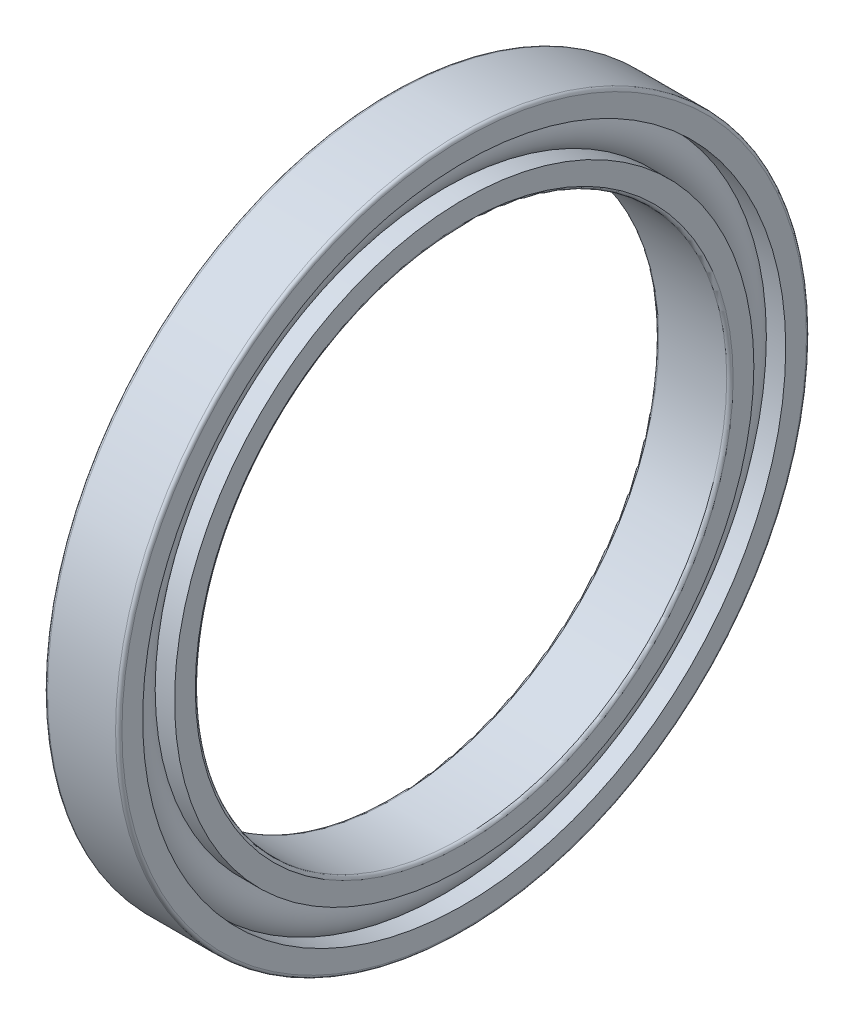
SolidWorks part; units mm, degrees
ref_plane "Plane1" through (0, 0, 0) normal (0, 0, 1) x (1, 0, 0)
ref_plane "Plane2" through (0, 0, 0) normal (0, 1, 0) x (1, 0, 0)
ref_plane "Plane3" through (0, 0, 0) normal (1, 0, 0) x (0, 0, -1)
sketch "Clipboard" plane through (0, 0, 0) normal (0, 0, 1) x (1, 0, 0)
  line L0 (-10, 0) -> (10, 0) construction
  line L1 (0, 0) -> (22.3471, -0.7804)
  line L2 (0, 0) -> (28.7325, 1.0034)
  line L3 (0, 0) -> (22.3471, -0.7804)
  line L4 (0, 0) -> (-22.3573, -0.3902)
  dimension "BallCLRad" = 28.75
sketch "CagSpiSke" plane through (0, 0, 0) normal (0, 0, 1) x (1, 0, 0)
  line L0 (0.225, 28.375) -> (0.225, 29.125)
  line L1 (0.225, 29.125) -> (-0.225, 29.125)
  line L2 (-0.225, 29.125) -> (-0.225, 28.375)
  line L3 (-0.225, 28.375) -> (0.225, 28.375)
  line L4 (-20.6375, 0) -> (20.6375, 0) construction
  line L5 (0, 0) -> (0, 23.7692) construction
  dimension "OD" = 58.25
  dimension "ID" = 56.75
revolve "CageSpine" add sketch "CagSpiSke" angle 0.001 about L4 reverse direction yes
ref_axis "Axis1" through (-50, 0, 0) along (1, 0, 0)
sketch "CagBalSke" plane through (0, 0, 0) normal (0, 0, 1) x (1, 0, 0)
  line L0 (-2.475, 28.75) -> (2.475, 28.75)
  line L1 (-1.905, 28.75) -> (1.905, 28.75) construction
  line L2 (-10, 0) -> (10, 0) construction
  line L3 (0, 0) -> (0, 24) construction
  arc A0 (2.475, 28.75) -> (-2.475, 28.75) centre (0, 28.75) cw
  dimension "BallCLRad" = 28.75
revolve "CageBall" [suppressed] add sketch "CagBalSke" angle 360 about L1 reverse direction yes
pattern_circular "CageBalls" [suppressed] count 2 every 180 about axis through (-50, 0, 0) along (1, 0, 0)
sketch "CagTrmODSke" plane through (0, 0, 0) normal (0, 0, 1) x (1, 0, 0)
  line L0 (2.476, 29.125) -> (2.476, 31.226)
  line L1 (2.476, 31.226) -> (-2.476, 31.226)
  line L2 (-2.476, 31.226) -> (-2.476, 29.125)
  line L3 (-2.476, 29.125) -> (2.476, 29.125)
  line L4 (-20.6375, 0) -> (20.6375, 0) construction
  line L5 (0, 0) -> (0, 25) construction
  dimension "Width" = 4.952
  dimension "ID" = 58.25
  dimension "OD" = 62.452
revolve "CageTrimOD" [suppressed] cut sketch "CagTrmODSke" angle 360 about L4 reverse direction yes
sketch "CagTrmIDSke" plane through (0, 0, 0) normal (0, 0, 1) x (1, 0, 0)
  line L0 (2.476, 26.276) -> (2.476, 28.375)
  line L1 (2.476, 28.375) -> (-2.476, 28.375)
  line L2 (-2.476, 28.375) -> (-2.476, 26.276)
  line L3 (-2.476, 26.276) -> (2.476, 26.276)
  line L4 (-20.6375, 0) -> (20.6375, 0) construction
  line L5 (0, 0) -> (0, 25) construction
  dimension "Width" = 4.952
  dimension "ID" = 52.552
  dimension "OD" = 56.75
revolve "CageTrimID" [suppressed] cut sketch "CagTrmIDSke" angle 360 about L4 reverse direction yes
sketch "BalSimSke" plane through (0, 0, 0) normal (0, 0, 1) x (1, 0, 0)
  line L0 (-10, 0) -> (10, 0) construction
  line L1 (-10, 28.75) -> (10, 28.75) construction
  line L2 (0, 0) -> (0, 23) construction
  circle A0 centre (0, 28.75) radius 2.25
  dimension "BallCLRad" = 28.75
  dimension "Ball_diameter" = 4.5
revolve "BallsSimplified" add sketch "BalSimSke" angle 360 about L0
sketch "BalDetSke" plane through (0, 0, 0) normal (0, 0, 1) x (1, 0, 0)
  line L0 (-2.25, 28.75) -> (2.25, 28.75)
  line L1 (-1.905, 28.75) -> (1.905, 28.75) construction
  line L2 (0, 0) -> (0, 25) construction
  arc A0 (2.25, 28.75) -> (-2.25, 28.75) centre (0, 28.75) cw
  dimension "BallCLRad" = 28.75
  dimension "Ball_diameter" = 4.5
revolve "BallDetailed" [suppressed] add sketch "BalDetSke" angle 360 about L1 reverse direction yes
sketch "InnRacSke" plane through (0, 0, 0) normal (0, 0, 1) x (1, 0, 0)
  line L0 (-1.6434, 27.25) -> (-3.5, 27.25)
  line L1 (-3.5, 27.25) -> (-3.5, 25.3)
  line L2 (-3.2, 25) -> (3.2, 25)
  line L3 (3.5, 25.3) -> (3.5, 27.25)
  line L4 (3.5, 27.25) -> (1.6434, 27.25)
  line L5 (-20.6375, 0) -> (20.6375, 0) construction
  line L6 (0, 0) -> (0, 30) construction
  arc A0 (-3.5, 25.3) -> (-3.2, 25) centre (-3.2, 25.3) ccw
  arc A1 (3.2, 25) -> (3.5, 25.3) centre (3.2, 25.3) ccw
  arc A2 (1.6434, 27.25) -> (-1.6434, 27.25) centre (0, 28.75) cw
  dimension "BallCLRad" = 28.75
  dimension "Fillet_radius" = 0.3
  dimension "Ball_diameter" = 4.45
  dimension "ID" = 50
  dimension "OD" = 54.5
  dimension "Width" = 7
revolve "InnerRace" add sketch "InnRacSke" angle 360 about L5 reverse direction yes
sketch "OutRacSke" plane through (0, 0, 0) normal (0, 0, 1) x (1, 0, 0)
  line L0 (-1.6434, 30.25) -> (-3.5, 30.25)
  line L1 (-3.5, 30.25) -> (-3.5, 32.2)
  line L2 (-3.2, 32.5) -> (3.2, 32.5)
  line L3 (3.5, 32.2) -> (3.5, 30.25)
  line L4 (3.5, 30.25) -> (1.6434, 30.25)
  line L5 (-20.6375, 0) -> (20.6375, 0) construction
  line L6 (0, 0) -> (0, 30) construction
  arc A0 (-3.5, 32.2) -> (-3.2, 32.5) centre (-3.2, 32.2) cw
  arc A1 (3.2, 32.5) -> (3.5, 32.2) centre (3.2, 32.2) cw
  arc A2 (1.6434, 30.25) -> (-1.6434, 30.25) centre (0, 28.75) ccw
  dimension "BallCLRad" = 28.75
  dimension "Fillet_radius" = 0.3
  dimension "Ball_diameter" = 4.45
  dimension "Width" = 7
revolve "OuterRace" add sketch "OutRacSke" angle 360 about L5 reverse direction yes
pattern_circular "BallsDetailed" [suppressed] count 2 every 180 about axis through (-50, 0, 0) along (1, 0, 0)
equation "\"BallCLRad@Clipboard\" = ( \"OD@OutRacSke\" + \"ID@InnRacSke\" ) / 4"
equation "\"BallCLRad@BalSimSke\" = \"BallCLRad@Clipboard\""
equation "\"BallCLRad@BalDetSke\" = \"BallCLRad@Clipboard\""
equation "\"BallCLRad@InnRacSke\" = \"BallCLRad@Clipboard\""
equation "\"BallCLRad@OutRacSke\" = \"BallCLRad@Clipboard\""
equation "\"Ball_diameter@InnRacSke\" = \"Ball_diameter@BalDetSke\" - 0.05"
equation "\"Ball_diameter@OutRacSke\" = \"Ball_diameter@BalDetSke\" - 0.05"
equation "\"Ball_diameter@BalSimSke\" = \"Ball_diameter@BalDetSke\""
equation "\"Width@OutRacSke\" = \"Width@InnRacSke\""
equation "\"Fillet_radius@OutRacSke\" = \"Fillet_radius@InnRacSke\""
equation "\"Max_count@Clipboard\" = int( 3.14159265 / atn(( \"Ball_diameter@BalDetSke\" / 2) / sqr( \"BallCLRad@Clipboard\"  *  \"BallCLRad@Clipboard\" - ( \"Ball_diameter@BalDetSke\" / 2) *  ( \"Ball_diameter@BalDetSke\" / 2))))"
equation "\"Max_count@Clipboard\" = ((sgn( \"Max_count@Clipboard\" - \"Count@Clipboard\" )-1)*( \"Max_count@Clipboard\" - \"Count@Clipboard\" ))/-2+ \"Count@Clipboard\""
equation "\"Count@BallsDetailed\" = int( \"Show_count@Clipboard\" ) "
equation "\"Count@BallsDetailed\" = ((sgn( \"Count@BallsDetailed\" - \"Max_count@Clipboard\" )-1)*( \"Count@BallsDetailed\" - \"Max_count@Clipboard\" ))/-2+ \"Max_count@Clipboard\""
equation "\"Count@BallsDetailed\" = ((sgn( \"Count@BallsDetailed\" - \"Min_count@Clipboard\" )+1)*( \"Count@BallsDetailed\" - \"Min_count@Clipboard\"))/2 +\"Min_count@Clipboard\""
equation "\"Angle@BallsDetailed\" = 360.0 / \"Max_count@Clipboard\""
equation "\"BallCLRad@CagBalSke\" = \"BallCLRad@Clipboard\""
equation "\"Count@CageBalls\" = \"Count@BallsDetailed\""
equation "\"Angle@CageBalls\" = \"Angle@BallsDetailed\""
equation "\"Angle@CageSpine\" =  \"Angle@CageBalls\" * ( \"Count@CageBalls\" -1 + int( \"Count@CageBalls\" / \"Max_count@Clipboard\" ) )  + 0.001 -  int( \"Count@CageBalls\" / \"Max_count@Clipboard\" ) * 0.001"
equation "\"Angle@CageSpine\" =  \"Angle@CageSpine\" * int( \"Min_count@Clipboard\" / 2) + int(1 / \"Min_count@Clipboard\")  * 0.001"
equation "\"CageWallOD@CagBalSke\" =  \"Ball_diameter@BalDetSke\" * 1.1"
equation "\"Thickness@CagSpiSke\" =  \"Ball_diameter@BalDetSke\" * 0.1"
equation "\"OD@CagTrmODSke\" = \"BallCLRad@Clipboard\" * 2 + \"CageWallOD@CagBalSke\" + 0.002"
equation "\"ID@CagTrmODSke\" = \"BallCLRad@Clipboard\" * 2 + \"Ball_diameter@BalDetSke\" / 6"
equation "\"OD@CagTrmIDSke\" = \"BallCLRad@Clipboard\" * 2 - \"Ball_diameter@BalDetSke\" / 6"
equation "\"ID@CagTrmIDSke\" = \"BallCLRad@Clipboard\" * 2 - \"CageWallOD@CagBalSke\" + 0.002"
equation "\"OD@CagSpiSke\" = \"ID@CagTrmODSke\""
equation "\"ID@CagSpiSke\" = \"OD@CagTrmIDSke\""
equation "\"Width@CagTrmODSke\" = \"CageWallOD@CagBalSke\" + 0.002"
equation "\"Width@CagTrmIDSke\" = \"CageWallOD@CagBalSke\" + 0.002"
